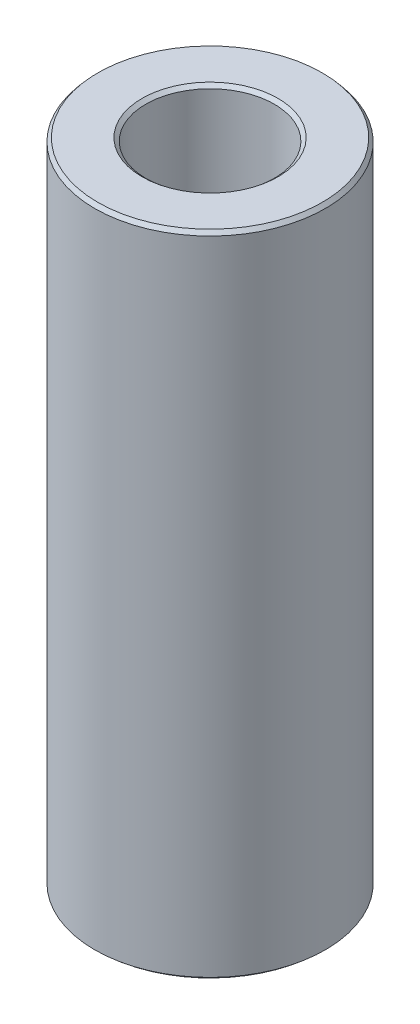
SolidWorks part; units mm, degrees
ref_plane "Front Plane" through (0, 0, 0) normal (0, 0, 1) x (1, 0, 0)
ref_plane "Top Plane" through (0, 0, 0) normal (0, 1, 0) x (1, 0, 0)
ref_plane "Right Plane" through (0, 0, 0) normal (1, 0, 0) x (0, 0, -1)
sketch "Sketch1" plane through (0, 0, 0) normal (0, 1, 0) x (1, 0, 0)
  circle A0 centre (0, 0) radius 30
  dimension "SLEEVE_OD" = 60
extrude "Boss-Extrude1" add sketch "Sketch1" along normal blind 168.759
sketch "Sketch2" plane through (0, 0, 0) normal (0, 1, 0) x (1, 0, 0)
  circle A0 centre (0, 0) radius 16.7113
  dimension "BORE_D" = 33.4227
extrude "Cut-Extrude1" cut sketch "Sketch2" along normal through all
chamfer "Chamfer1" distance 0.97 angle 40.066 4 edges at (0, 168.759, 16.7113) (0, 0, 16.7113) (0, 0, 30) (0, 168.759, 30) first distance on face at (0, 168.759, 16.7113) first distance on face at (0, 0, 16.7113) first distance on face at (0, 168.759, 30)
